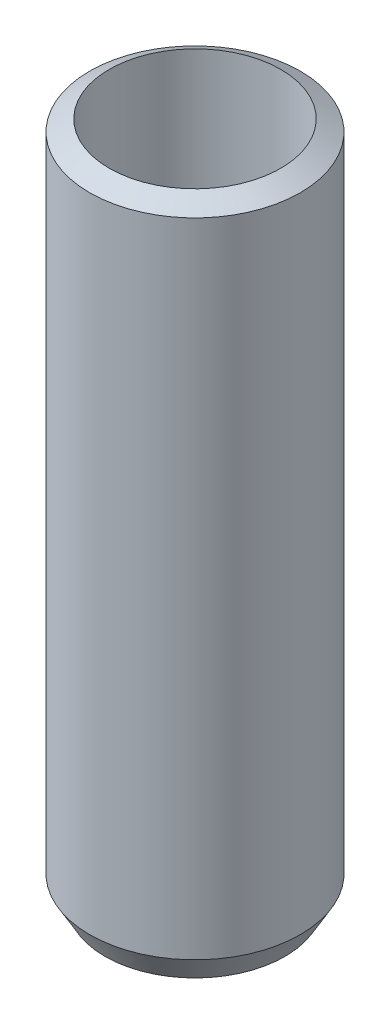
SolidWorks part; units mm, degrees
ref_plane "Front Plane" through (0, 0, 0) normal (0, 0, 1) x (1, 0, 0)
ref_plane "Top Plane" through (0, 0, 0) normal (0, 1, 0) x (1, 0, 0)
ref_plane "Right Plane" through (0, 0, 0) normal (1, 0, 0) x (0, 0, -1)
sketch "Sketch1" plane through (0, 0, 0) normal (0, 1, 0) x (1, 0, 0)
  circle A0 centre (0, 0) radius 40
  dimension "SHAFT_OD" = 80
extrude "Boss-Extrude1" add sketch "Sketch1" along normal blind 259.8741
sketch "Sketch2" plane through (0, 0, 0) normal (0, 1, 0) x (1, 0, 0)
  circle A0 centre (0, 0) radius 32.5541
  dimension "BORE_D" = 65.1082
extrude "Cut-Extrude1" cut sketch "Sketch2" along normal through all
chamfer "Chamfer1" distance 5.8269 angle 60 2 edges at (0, 259.8741, 40) (0, 0, 40) first distance on face at (0, 259.8741, 40) first distance on face at (0, 0, 32.5541)
